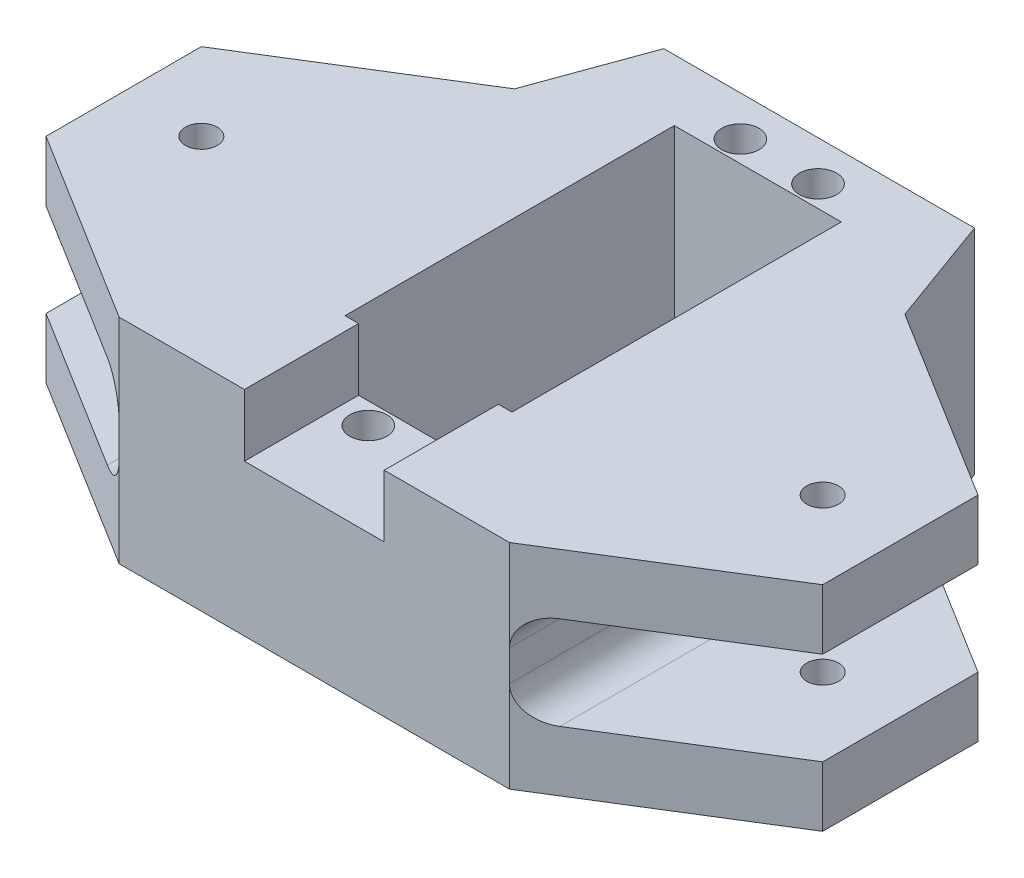
SolidWorks part; units mm, degrees
ref_plane "Front Plane" through (0, 0, 0) normal (0, 0, 1) x (1, 0, 0)
ref_plane "Top Plane" through (0, 0, 0) normal (0, 1, 0) x (1, 0, 0)
ref_plane "Right Plane" through (0, 0, 0) normal (1, 0, 0) x (0, 0, -1)
sketch "Sketch1" plane through (0, 0, 0) normal (0, 1, 0) x (1, 0, 0)
  line L0 (0, 0) -> (0, 55585.7092) construction
  line L1 (0, 0) -> (55585.7092, 0) construction
  line L2 (20, 39.5477) -> (-20, 39.5477)
  line L3 (-20, 39.5477) -> (-25.1303, 25.4523)
  line L4 (-25.1303, 25.4523) -> (-50, 10)
  line L5 (-50, 10) -> (-50, -10)
  line L11 (50, 10) -> (50, -10)
  line L12 (25.1303, 25.4523) -> (50, 10)
  line L13 (20, 39.5477) -> (25.1303, 25.4523)
  line L14 (25.1303, -25.4523) -> (50, -10)
  line L15 (-25.1303, -25.4523) -> (-50, -10)
  line L19 (25.1303, -25.4523) -> (-25.1303, -25.4523)
  point P7 (50, 0)
  point P12 (-50, 0)
  point P14 (0, -10.7407)
  point P19 (0, 39.5477)
  dimension "D1" = 40
  dimension "D2" = 20
  dimension "D3" = 65
  dimension "D4" = 100
  dimension "D5" = 110
  dimension "D8" = 15
extrude "Main-Body" add sketch "Sketch1" along normal mid plane 27.5
sketch "Sketch2" plane through (0, 13.75, 0) normal (0, 1, 0) x (1, 0, 0)
  line L0 (0, 47.5477) -> (0, -49952.4523) construction
  line L1 (-50, 0) -> (49950, 0) construction
  line L2 (20, 39.5477) -> (-20, 39.5477) construction
  line L3 (-10, 10.45) -> (10, 10.45) construction
  line L4 (10, -10) -> (-10, -10) construction
  line L5 (-10, -10) -> (-10, 30.9) construction
  line L6 (-10, 30.9) -> (10, 30.9) construction
  line L7 (10, -10) -> (10, 30.9) construction
  line L8 (0, -25.4523) -> (50000, -25.4523) construction
  line L9 (-50, 10) -> (-50, -10) construction
  line L10 (-5, 34.4) -> (5, 34.4) construction
  line L11 (-5, -13.5) -> (5, -13.5) construction
  line L12 (-25.1303, -25.4523) -> (25.1303, -25.4523) construction
  line L14 (-10.75, 31.65) -> (10.75, 31.65)
  line L15 (-10.75, 31.65) -> (-10.75, -10.75)
  line L16 (-10.75, -10.75) -> (10.75, -10.75)
  line L17 (10.75, 31.65) -> (10.75, -10.75)
  line L18 (-10.75, 31.65) -> (10.75, -10.75) construction
  line L19 (-10.75, -10.75) -> (10.75, 31.65) construction
  circle A0 centre (-5, -13.5) radius 2.4
  circle A1 centre (5, -13.5) radius 2.4
  circle A2 centre (-5, 34.4) radius 2.4
  circle A3 centre (5, 34.4) radius 2.4
  circle A4 centre (0, 0) radius 2 construction
  circle A5 centre (-40, 0) radius 2.05
  circle A6 centre (40, 0) radius 2.05
  point P22 (0, -10)
  point P23 (0, 30.9)
  point P28 (0, 39.5477)
  point P29 (0, -13.5)
  point P30 (0, 34.4)
  point P31 (-50, 0)
  point P32 (0, 10.45)
  point P39 (0, 0)
  dimension "D1" = 4.8
  dimension "D4" = 4.8
  dimension "D10" = 4.8
  dimension "D11" = 4.8
  dimension "D13" = 4
  dimension "D16" = 4.1
  dimension "D3" = 10
  dimension "D6" = 10
  dimension "D7" = 20
  dimension "D8" = 3.5
  dimension "D9" = 3.5
  dimension "D5" = 40.9
  dimension "D2" = 0.75
  dimension "D12" = 0.75
  dimension "D14" = 10
  dimension "D15" = 0
  dimension "D17" = 10
extrude "Servo&RotRod-Cutout" cut sketch "Sketch2" against normal blind 30
sketch "Sketch3" plane through (0, 0, 25.4523) normal (0, 0, 1) x (1, 0, 0)
  line L0 (0, 0) -> (0, 50000) construction
  line L1 (0, 0) -> (48695.3801, 0) construction
  line L3 (9, 13.75) -> (-9, 13.75)
  line L4 (-9, 13.75) -> (-9, 5.75)
  line L5 (-9, 5.75) -> (9, 5.75)
  line L6 (9, 13.75) -> (9, 5.75)
  line L7 (-25.1303, 13.75) -> (25.1303, 13.75) construction
  point P10 (0, 0)
  point P11 (0, 13.75)
  dimension "D1" = 18
  dimension "D2" = 8
  dimension "D3" = 0
extrude "Servo-Cable-Cutout" cut sketch "Sketch3" against normal up to surface (14.7023 mm away) up to face at (0, 0, 10.75)
sketch "Sketch4" plane through (0, 0, 25.4523) normal (0, 0, 1) x (1, 0, 0)
  line L0 (0, 0) -> (0, 50000) construction
  line L1 (50, 0) -> (50050, 0) construction
  line L2 (50, 13.75) -> (50, -13.75) construction
  line L3 (-50, -6) -> (-50, 6)
  line L4 (-50, 13.75) -> (-50, -13.75) construction
  line L5 (-50, 6) -> (-25.1303, 6)
  line L6 (-25.1303, 6) -> (-25.1303, -6)
  line L7 (-50, -6) -> (-25.1303, -6)
  line L10 (-25.1303, 13.75) -> (-25.1303, -13.75) construction
  point P7 (50, 0)
  point P15 (-25.1303, 0)
  point P16 (-50, 0)
  dimension "D1" = 0
  dimension "D2" = 12
extrude "Control-Arm-Cutout" cut sketch "Sketch4" against normal through all both and the other way through all
mirror "Mirror1" about plane through (0, 0, 0) normal (1, 0, 0) of "Control-Arm-Cutout"
sketch "Sketch5" plane through (0, 13.75, 0) normal (0, 1, 0) x (1, 0, 0)
  line L0 (-50, 0) -> (49950, 0) construction
  line L1 (-50, 10) -> (-50, -10) construction
  line L2 (0, 0) -> (0, 50000) construction
  circle A0 centre (-40, 0) radius 2.05
  point P4 (-50, 0)
  dimension "D1" = 4.1
  dimension "D2" = 10
extrude "Cut-Extrude4" [suppressed] cut sketch "Sketch5" against normal through all both and the other way through all
mirror "Mirror2" [suppressed] about plane through (0, 0, 0) normal (1, 0, 0)
fillet "Fillet1" radius 4 4 edges at (-25.1303, -6, 0) (-25.1303, 6, 0) (25.1303, -6, 0) (25.1303, 6, 0)
equation "\"D10@Sketch2\"=\"D1@Sketch2\""
equation "\"D11@Sketch2\"=\"D1@Sketch2\""
